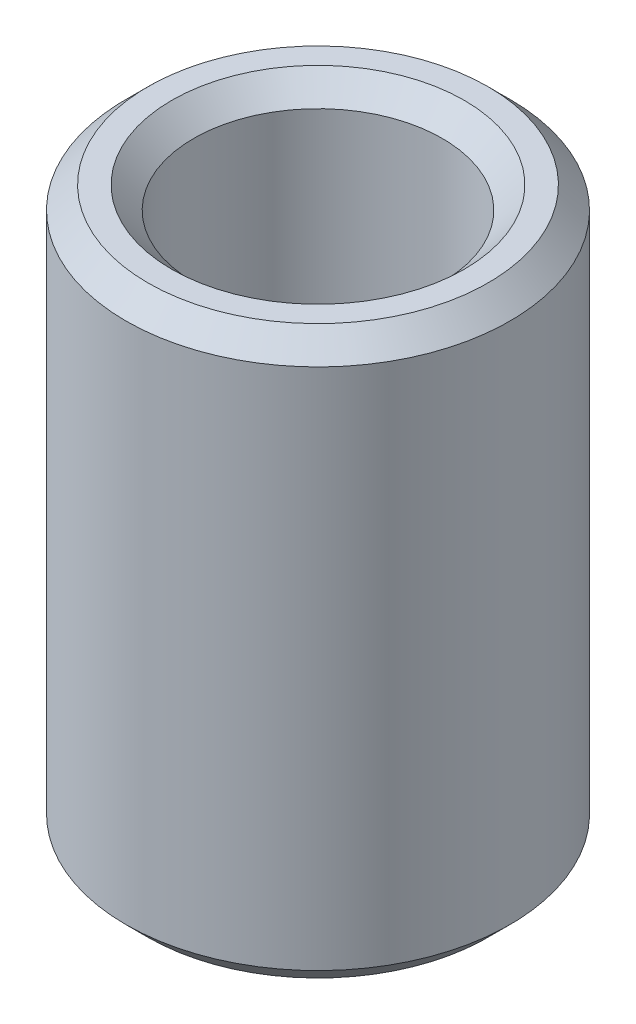
SolidWorks part; units mm, degrees
ref_plane "Front Plane" through (0, 0, 0) normal (0, 0, 1) x (1, 0, 0)
ref_plane "Top Plane" through (0, 0, 0) normal (0, 1, 0) x (1, 0, 0)
ref_plane "Right Plane" through (0, 0, 0) normal (1, 0, 0) x (0, 0, -1)
sketch "Sketch1" plane through (0, 0, 0) normal (0, 1, 0) x (1, 0, 0)
  circle A0 centre (0, 0) radius 7.5
  dimension "SLEEVE_OD" = 15
extrude "Boss-Extrude1" add sketch "Sketch1" along normal blind 22.1363
sketch "Sketch2" plane through (0, 0, 0) normal (0, 1, 0) x (1, 0, 0)
  circle A0 centre (0, 0) radius 4.8568
  dimension "BORE_D" = 9.7136
extrude "Cut-Extrude1" cut sketch "Sketch2" along normal through all
chamfer "Chamfer1" distance 0.8584 angle 45 4 edges at (0, 22.1363, 4.8568) (0, 0, 4.8568) (0, 0, 7.5) (0, 22.1363, 7.5)
